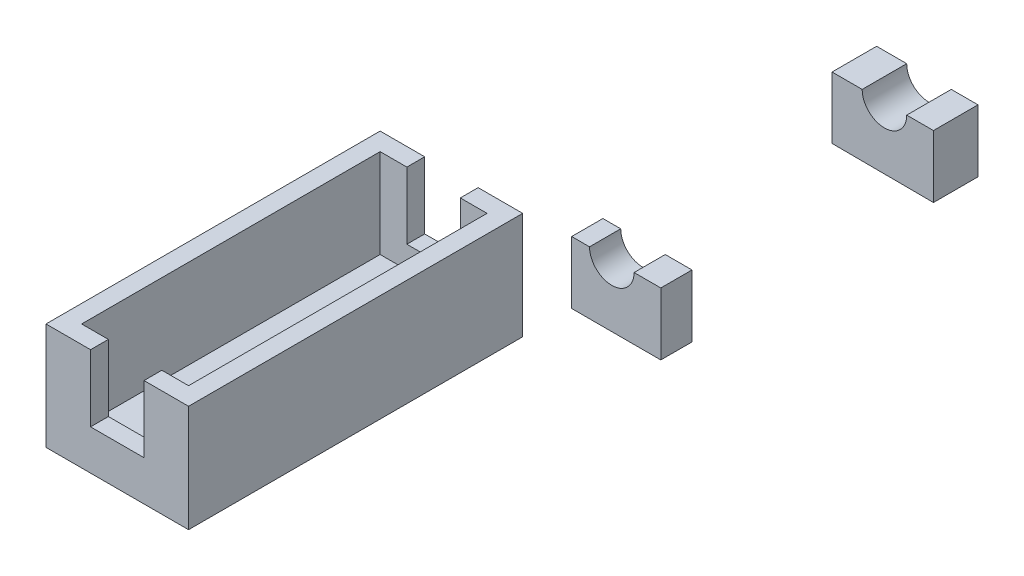
SolidWorks part; units mm, degrees
ref_plane "Front Plane" through (0, 0, 0) normal (0, 0, 1) x (1, 0, 0)
ref_plane "Top Plane" through (0, 0, 0) normal (0, 1, 0) x (1, 0, 0)
ref_plane "Right Plane" through (0, 0, 0) normal (1, 0, 0) x (0, 0, -1)
sketch "Sketch1" plane through (0, 0, 0) normal (0, 0, 1) x (1, 0, 0)
  line L0 (0, 0) -> (-12.5, 0) construction
  line L1 (0, 0) -> (0, -5) construction
  line L2 (0, -5) -> (6, -5) construction
  line L3 (6, -5) -> (-6, -5)
  line L4 (0, -2.5) -> (3, -2.5)
  line L5 (0, -2.5) -> (-3, -2.5)
  line L6 (6, -5) -> (6, 5)
  line L7 (-3, -2.5) -> (-3, 5)
  line L8 (3, -2.5) -> (3, 5)
  line L9 (3, 5) -> (6, 5)
  line L10 (6, 5) -> (8, 5)
  line L11 (8, 5) -> (8, -7)
  line L12 (8, -7) -> (-8, -7)
  line L13 (-8, -7) -> (-8, 5)
  line L14 (-8, 5) -> (-6, 5)
  line L15 (-6, 5) -> (-6, -5)
  line L16 (-3, 5) -> (-6, 5)
  line L17 (-3, 5) -> (3, 5)
  circle A0 centre (0, 0) radius 1.5 construction
  circle A1 centre (-12.5, 0) radius 1 construction
  dimension "D2" = 3
  dimension "D3" = 2
  dimension "D1" = 12.5
  dimension "D4" = 5
  dimension "D5" = 6
  dimension "D6" = 12
  dimension "D7" = 3
  dimension "D8" = 10
  dimension "D9" = 2
  dimension "D10" = 12
  dimension "D11" = 16
extrude "Boss-Extrude1" add sketch "Sketch1" along normal blind 33.5 contours L15 L14 L13 L12 L11 L10 L6 L3 region at (6.2, 0, 0)
extrude "Boss-Extrude2" add sketch "Sketch1<3>" against normal blind 2 contours L7 L16 L15 L3 L6 L9 L8 L4 L5 | L15 L14 L13 L12 L11 L10 L6 L3 region at (6.2, 0, 0) region at (0, -4.8438, 0)
sketch "Sketch1<3>" plane through (0, 0, 0) normal (0, 0, 1) x (1, 0, 0) same geometry as "Sketch1"
extrude "Boss-Extrude3" add sketch "Sketch1<4>" along normal blind 2 from surface contours L7 L16 L15 L3 L6 L9 L8 L4 L5 | L15 L14 L13 L12 L11 L10 L6 L3 region at (6.2, 0, 0) region at (0, -4.8438, 0) starting at face at (0, -0.5, 33.5)
sketch "Sketch1<4>" plane through (0, 0, 0) normal (0, 0, 1) x (1, 0, 0) same geometry as "Sketch1"
sketch "Sketch3" plane through (0, 0, -2) normal (0, 0, -1) x (-1, 0, 0)
  line L0 (0, 0) -> (-12.5, 0) construction
  line L1 (-15, 0) -> (-18, 0)
  line L2 (-10, 0) -> (-7, 0)
  line L3 (-18, 0) -> (-18, -7)
  line L4 (-18, -7) -> (-7, -7)
  line L5 (8, -7) -> (-8, -7) construction
  line L6 (-7, -7) -> (-7, 0)
  line L7 (-10, 0) -> (-15, 0) construction
  arc A2 (-10, 0) -> (-15, 0) centre (-12.5, 0) cw
  line M11 (-8, 5) -> (-8, -7)
  dimension "D1" = 12.5
  dimension "D3" = 3
  dimension "D4" = 3
  dimension "D5" = 7
extrude "Boss-Extrude4" add sketch "Sketch3" along normal blind 3.5 from offset 5.5 separate body contours L2 A2 L1 L3 L4 M11 region at (13.0816, -3.8979, -2)
ref_plane "Plane1" through (0, 0, -38.1) normal (0, 0, -1) x (-1, 0, 0)
sketch "Sketch4" plane through (0, 0, -38.1) normal (0, 0, -1) x (-1, 0, 0)
  line L0 (-15, 0) -> (-18, 0)
  line L1 (-18, 0) -> (-18, -7)
  line L2 (-18, 0) -> (-18, -7) construction
  line L3 (-18, -7) -> (-6.6208, -6.9458)
  line L4 (-6.6208, -6.9458) -> (-6.6208, 0)
  line L5 (-6.6208, 0) -> (-10, 0)
  arc A0 (-6.7691, -7.0687) -> (-6.4751, -6.8199) centre (-12.5, 0) ccw construction
  circle A1 centre (-12.5, 0) radius 2.5 construction
  arc A2 (-10, 0) -> (-15, 0) centre (-12.5, 0) cw
  arc A3 (-15, 0) -> (-10, 0) centre (-12.5, 0) ccw construction
extrude "Boss-Extrude5" add sketch "Sketch4" along normal blind 5 separate body contours L5 A2 L0 L1 L3 L4 region at (12.292, -3.8289, -38.1)
